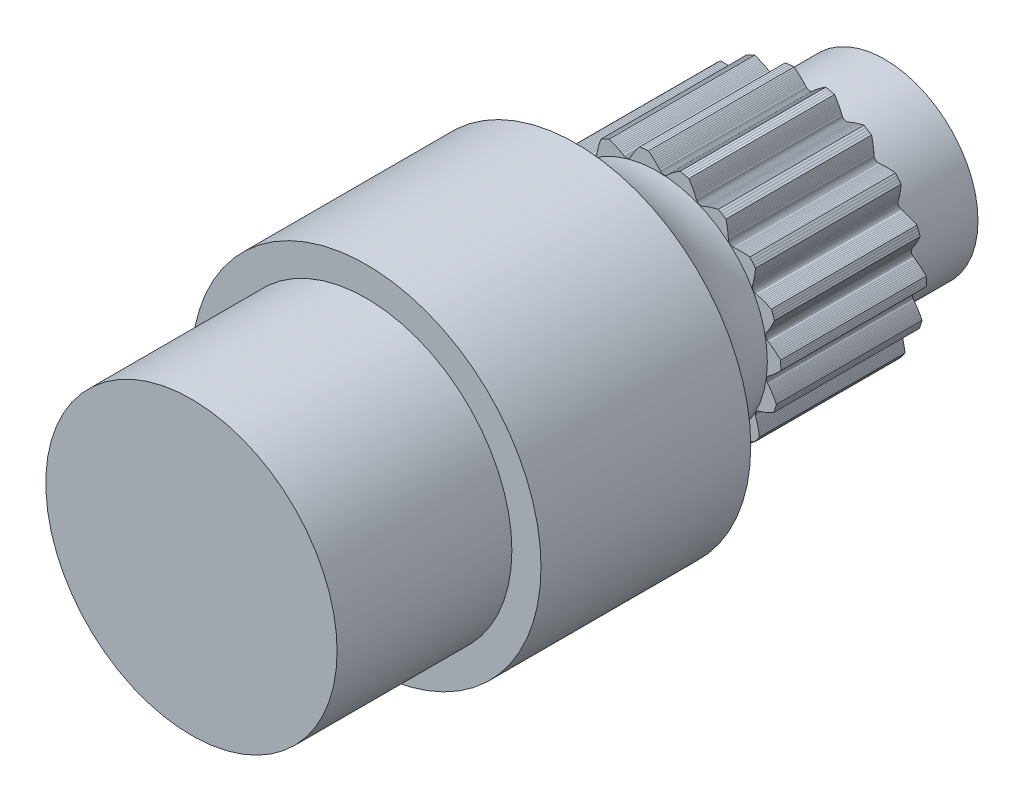
SolidWorks part; units mm, degrees
ref_plane "Front Plane" through (0, 0, 0) normal (0, 0, 1) x (1, 0, 0)
ref_plane "Top Plane" through (0, 0, 0) normal (0, 1, 0) x (1, 0, 0)
ref_plane "Right Plane" through (0, 0, 0) normal (1, 0, 0) x (0, 0, -1)
sketch "19T Shaft" plane through (0, 0, 0) normal (0, 0, 1) x (1, 0, 0)
  point P0 (-10.5755, 0)
  line B0 (6.0231, -8.6927) -> (5.8644, -8.8006)
  line B1 (5.8644, -8.8006) -> (5.7037, -8.9056)
  line B2 (5.7037, -8.9056) -> (5.5745, -8.8826)
  line B3 (5.5745, -8.8826) -> (5.4476, -8.8579)
  line B4 (5.4476, -8.8579) -> (5.3232, -8.8314)
  line B5 (5.3232, -8.8314) -> (5.1984, -8.8027)
  line B6 (5.1984, -8.8027) -> (5.0761, -8.7722)
  line B7 (5.0761, -8.7722) -> (4.9565, -8.7403)
  line B8 (4.9565, -8.7403) -> (4.8368, -8.706)
  line B9 (4.8368, -8.706) -> (4.7198, -8.6703)
  line B10 (4.7198, -8.6703) -> (4.603, -8.6323)
  line B11 (4.603, -8.6323) -> (4.4891, -8.593)
  line B12 (4.4891, -8.593) -> (4.3274, -8.5331)
  line B13 (4.3274, -8.5331) -> (4.2909, -8.5213)
  line B14 (4.2909, -8.5213) -> (4.254, -8.5136)
  line B15 (4.254, -8.5136) -> (4.2158, -8.5099)
  line B16 (4.2158, -8.5099) -> (4.1778, -8.5104)
  line B17 (4.1778, -8.5104) -> (4.1402, -8.515)
  line B18 (4.1402, -8.515) -> (4.1034, -8.5237)
  line B19 (4.1034, -8.5237) -> (4.0679, -8.5363)
  line B20 (4.0679, -8.5363) -> (4.0531, -8.5429)
  line B21 (4.0531, -8.5429) -> (4.0429, -8.5478)
  line B22 (4.0429, -8.5478) -> (4.0326, -8.5526)
  line B23 (4.0326, -8.5526) -> (4.0223, -8.5575)
  line B24 (4.0223, -8.5575) -> (4.012, -8.5623)
  line B25 (4.012, -8.5623) -> (3.9976, -8.5695)
  line B26 (3.9976, -8.5695) -> (3.9652, -8.5889)
  line B27 (3.9652, -8.5889) -> (3.9351, -8.6117)
  line B28 (3.9351, -8.6117) -> (3.9076, -8.6377)
  line B29 (3.9076, -8.6377) -> (3.883, -8.6668)
  line B30 (3.883, -8.6668) -> (3.8616, -8.6986)
  line B31 (3.8616, -8.6986) -> (3.8441, -8.732)
  line B32 (3.8441, -8.732) -> (3.83, -8.7676)
  line B33 (3.83, -8.7676) -> (3.7733, -8.9305)
  line B34 (3.7733, -8.9305) -> (3.7312, -9.0434)
  line B35 (3.7312, -9.0434) -> (3.6862, -9.1576)
  line B36 (3.6862, -9.1576) -> (3.6393, -9.2706)
  line B37 (3.6393, -9.2706) -> (3.5895, -9.3848)
  line B38 (3.5895, -9.3848) -> (3.5381, -9.4975)
  line B39 (3.5381, -9.4975) -> (3.4838, -9.6111)
  line B40 (3.4838, -9.6111) -> (3.4265, -9.7257)
  line B41 (3.4265, -9.7257) -> (3.3678, -9.8385)
  line B42 (3.3678, -9.8385) -> (3.3062, -9.9521)
  line B43 (3.3062, -9.9521) -> (3.2417, -10.0664)
  line B44 (3.2417, -10.0664) -> (3.0585, -10.1236)
  line B45 (3.0585, -10.1236) -> (2.8742, -10.1774)
  line B46 (8.5193, -6.266) -> (8.4042, -6.4196)
  line B47 (8.4042, -6.4196) -> (8.2863, -6.5711)
  line B48 (8.2863, -6.5711) -> (8.1566, -6.5913)
  line B49 (8.1566, -6.5913) -> (8.0286, -6.6091)
  line B50 (8.0286, -6.6091) -> (7.9024, -6.6245)
  line B51 (7.9024, -6.6245) -> (7.775, -6.6378)
  line B52 (7.775, -6.6378) -> (7.6495, -6.6487)
  line B53 (7.6495, -6.6487) -> (7.5259, -6.6573)
  line B54 (7.5259, -6.6573) -> (7.4015, -6.6638)
  line B55 (7.4015, -6.6638) -> (7.2793, -6.668)
  line B56 (7.2793, -6.668) -> (7.1565, -6.67)
  line B57 (7.1565, -6.67) -> (7.036, -6.6698)
  line B58 (7.036, -6.6698) -> (6.8636, -6.6657)
  line B59 (6.8636, -6.6657) -> (6.8253, -6.6663)
  line B60 (6.8253, -6.6663) -> (6.7879, -6.671)
  line B61 (6.7879, -6.671) -> (6.7506, -6.6799)
  line B62 (6.7506, -6.6799) -> (6.7147, -6.6927)
  line B63 (6.7147, -6.6927) -> (6.6807, -6.7093)
  line B64 (6.6807, -6.7093) -> (6.6487, -6.7295)
  line B65 (6.6487, -6.7295) -> (6.6192, -6.753)
  line B66 (6.6192, -6.753) -> (6.6074, -6.764)
  line B67 (6.6074, -6.764) -> (6.5993, -6.7719)
  line B68 (6.5993, -6.7719) -> (6.5911, -6.7798)
  line B69 (6.5911, -6.7798) -> (6.583, -6.7878)
  line B70 (6.583, -6.7878) -> (6.5748, -6.7957)
  line B71 (6.5748, -6.7957) -> (6.5635, -6.8072)
  line B72 (6.5635, -6.8072) -> (6.5392, -6.836)
  line B73 (6.5392, -6.836) -> (6.5181, -6.8673)
  line B74 (6.5181, -6.8673) -> (6.5006, -6.9009)
  line B75 (6.5006, -6.9009) -> (6.4867, -6.9364)
  line B76 (6.4867, -6.9364) -> (6.4768, -6.9734)
  line B77 (6.4768, -6.9734) -> (6.4711, -7.0107)
  line B78 (6.4711, -7.0107) -> (6.4693, -7.049)
  line B79 (6.4693, -7.049) -> (6.4686, -7.2215)
  line B80 (6.4686, -7.2215) -> (6.4654, -7.3419)
  line B81 (6.4654, -7.3419) -> (6.4599, -7.4646)
  line B82 (6.4599, -7.4646) -> (6.4523, -7.5866)
  line B83 (6.4523, -7.5866) -> (6.4423, -7.7108)
  line B84 (6.4423, -7.7108) -> (6.4302, -7.834)
  line B85 (6.4302, -7.834) -> (6.4157, -7.9592)
  line B86 (6.4157, -7.9592) -> (6.3988, -8.0862)
  line B87 (6.3988, -8.0862) -> (6.3799, -8.2119)
  line B88 (6.3799, -8.2119) -> (6.3585, -8.3394)
  line B89 (6.3585, -8.3394) -> (6.3346, -8.4684)
  line B90 (6.3346, -8.4684) -> (6.1799, -8.582)
  line B91 (6.1799, -8.582) -> (6.0231, -8.6927)
  line B92 (10.0923, -3.1603) -> (10.0332, -3.3429)
  line B93 (10.0332, -3.3429) -> (9.9709, -3.5245)
  line B94 (9.9709, -3.5245) -> (9.8549, -3.5857)
  line B95 (9.8549, -3.5857) -> (9.7396, -3.6441)
  line B96 (9.7396, -3.6441) -> (9.6252, -3.6997)
  line B97 (9.6252, -3.6997) -> (9.509, -3.7536)
  line B98 (9.509, -3.7536) -> (9.3938, -3.8047)
  line B99 (9.3938, -3.8047) -> (9.2797, -3.853)
  line B100 (9.2797, -3.853) -> (9.1642, -3.8995)
  line B101 (9.1642, -3.8995) -> (9.05, -3.9431)
  line B102 (9.05, -3.9431) -> (8.9345, -3.9849)
  line B103 (8.9345, -3.9849) -> (8.8205, -4.0238)
  line B104 (8.8205, -4.0238) -> (8.6561, -4.0759)
  line B105 (8.6561, -4.0759) -> (8.62, -4.089)
  line B106 (8.62, -4.089) -> (8.5862, -4.1055)
  line B107 (8.5862, -4.1055) -> (8.5538, -4.1261)
  line B108 (8.5538, -4.1261) -> (8.524, -4.1498)
  line B109 (8.524, -4.1498) -> (8.4972, -4.1766)
  line B110 (8.4972, -4.1766) -> (8.4735, -4.206)
  line B111 (8.4735, -4.206) -> (8.4533, -4.2378)
  line B112 (8.4533, -4.2378) -> (8.4457, -4.2521)
  line B113 (8.4457, -4.2521) -> (8.4405, -4.2622)
  line B114 (8.4405, -4.2622) -> (8.4354, -4.2723)
  line B115 (8.4354, -4.2723) -> (8.4303, -4.2825)
  line B116 (8.4303, -4.2825) -> (8.4251, -4.2926)
  line B117 (8.4251, -4.2926) -> (8.4181, -4.3072)
  line B118 (8.4181, -4.3072) -> (8.4045, -4.3423)
  line B119 (8.4045, -4.3423) -> (8.3948, -4.3788)
  line B120 (8.3948, -4.3788) -> (8.3891, -4.4163)
  line B121 (8.3891, -4.4163) -> (8.3875, -4.4543)
  line B122 (8.3875, -4.4543) -> (8.3902, -4.4926)
  line B123 (8.3902, -4.4926) -> (8.3968, -4.5297)
  line B124 (8.3968, -4.5297) -> (8.4076, -4.5665)
  line B125 (8.4076, -4.5665) -> (8.4629, -4.7298)
  line B126 (8.4629, -4.7298) -> (8.499, -4.8448)
  line B127 (8.499, -4.8448) -> (8.5336, -4.9626)
  line B128 (8.5336, -4.9626) -> (8.566, -5.0805)
  line B129 (8.566, -5.0805) -> (8.5969, -5.2012)
  line B130 (8.5969, -5.2012) -> (8.6255, -5.3217)
  line B131 (8.6255, -5.3217) -> (8.6525, -5.4448)
  line B132 (8.6525, -5.4448) -> (8.6777, -5.5704)
  line B133 (8.6777, -5.5704) -> (8.7006, -5.6954)
  line B134 (8.7006, -5.6954) -> (8.7218, -5.8229)
  line B135 (8.7218, -5.8229) -> (8.7411, -5.9527)
  line B136 (8.7411, -5.9527) -> (8.6316, -6.1104)
  line B137 (8.6316, -6.1104) -> (8.5193, -6.266)
  line B138 (10.5716, 0.2879) -> (10.5751, 0.096)
  line B139 (10.5751, 0.096) -> (10.5751, -0.096)
  line B140 (10.5751, -0.096) -> (10.4852, -0.1916)
  line B141 (10.4852, -0.1916) -> (10.3951, -0.2842)
  line B142 (10.3951, -0.2842) -> (10.3049, -0.3739)
  line B143 (10.3049, -0.3739) -> (10.2126, -0.4627)
  line B144 (10.2126, -0.4627) -> (10.1202, -0.5484)
  line B145 (10.1202, -0.5484) -> (10.028, -0.6311)
  line B146 (10.028, -0.6311) -> (9.9338, -0.7126)
  line B147 (9.9338, -0.7126) -> (9.8399, -0.791)
  line B148 (9.8399, -0.791) -> (9.7443, -0.868)
  line B149 (9.7443, -0.868) -> (9.6491, -0.9418)
  line B150 (9.6491, -0.9418) -> (9.5105, -1.0445)
  line B151 (9.5105, -1.0445) -> (9.4807, -1.0685)
  line B152 (9.4807, -1.0685) -> (9.454, -1.0952)
  line B153 (9.454, -1.0952) -> (9.43, -1.1251)
  line B154 (9.43, -1.1251) -> (9.4096, -1.1573)
  line B155 (9.4096, -1.1573) -> (9.3929, -1.1913)
  line B156 (9.3929, -1.1913) -> (9.3801, -1.2268)
  line B157 (9.3801, -1.2268) -> (9.3712, -1.2634)
  line B158 (9.3712, -1.2634) -> (9.3687, -1.2794)
  line B159 (9.3687, -1.2794) -> (9.3671, -1.2906)
  line B160 (9.3671, -1.2906) -> (9.3656, -1.3019)
  line B161 (9.3656, -1.3019) -> (9.364, -1.3131)
  line B162 (9.364, -1.3131) -> (9.3624, -1.3244)
  line B163 (9.3624, -1.3244) -> (9.3605, -1.3404)
  line B164 (9.3605, -1.3404) -> (9.3591, -1.3781)
  line B165 (9.3591, -1.3781) -> (9.3617, -1.4158)
  line B166 (9.3617, -1.4158) -> (9.3685, -1.4531)
  line B167 (9.3685, -1.4531) -> (9.3794, -1.4895)
  line B168 (9.3794, -1.4895) -> (9.3943, -1.5249)
  line B169 (9.3943, -1.5249) -> (9.4126, -1.5578)
  line B170 (9.4126, -1.5578) -> (9.4348, -1.5891)
  line B171 (9.4348, -1.5891) -> (9.5401, -1.7256)
  line B172 (9.5401, -1.7256) -> (9.6116, -1.8226)
  line B173 (9.6116, -1.8226) -> (9.6826, -1.9228)
  line B174 (9.6826, -1.9228) -> (9.7515, -2.0239)
  line B175 (9.7515, -2.0239) -> (9.8199, -2.128)
  line B176 (9.8199, -2.128) -> (9.8861, -2.2327)
  line B177 (9.8861, -2.2327) -> (9.9516, -2.3403)
  line B178 (9.9516, -2.3403) -> (10.0162, -2.4509)
  line B179 (10.0162, -2.4509) -> (10.0785, -2.5618)
  line B180 (10.0785, -2.5618) -> (10.1399, -2.6755)
  line B181 (10.1399, -2.6755) -> (10.2003, -2.792)
  line B182 (10.2003, -2.792) -> (10.1479, -2.9766)
  line B183 (10.1479, -2.9766) -> (10.0923, -3.1603)
  line B184 (9.9053, 3.7049) -> (9.9709, 3.5245)
  line B185 (9.9709, 3.5245) -> (10.0332, 3.3429)
  line B186 (10.0332, 3.3429) -> (9.9793, 3.2233)
  line B187 (9.9793, 3.2233) -> (9.9242, 3.1065)
  line B188 (9.9242, 3.1065) -> (9.868, 2.9924)
  line B189 (9.868, 2.9924) -> (9.8094, 2.8784)
  line B190 (9.8094, 2.8784) -> (9.7499, 2.7674)
  line B191 (9.7499, 2.7674) -> (9.6896, 2.6592)
  line B192 (9.6896, 2.6592) -> (9.627, 2.5516)
  line B193 (9.627, 2.5516) -> (9.5636, 2.4469)
  line B194 (9.5636, 2.4469) -> (9.4981, 2.343)
  line B195 (9.4981, 2.343) -> (9.4321, 2.2423)
  line B196 (9.4321, 2.2423) -> (9.3343, 2.1002)
  line B197 (9.3343, 2.1002) -> (9.3139, 2.0678)
  line B198 (9.3139, 2.0678) -> (9.2974, 2.0339)
  line B199 (9.2974, 2.0339) -> (9.2844, 1.9978)
  line B200 (9.2844, 1.9978) -> (9.2755, 1.9607)
  line B201 (9.2755, 1.9607) -> (9.2708, 1.9232)
  line B202 (9.2708, 1.9232) -> (9.2702, 1.8854)
  line B203 (9.2702, 1.8854) -> (9.2737, 1.8479)
  line B204 (9.2737, 1.8479) -> (9.2765, 1.832)
  line B205 (9.2765, 1.832) -> (9.2787, 1.8208)
  line B206 (9.2787, 1.8208) -> (9.2809, 1.8097)
  line B207 (9.2809, 1.8097) -> (9.283, 1.7985)
  line B208 (9.283, 1.7985) -> (9.2852, 1.7873)
  line B209 (9.2852, 1.7873) -> (9.2886, 1.7716)
  line B210 (9.2886, 1.7716) -> (9.2994, 1.7354)
  line B211 (9.2994, 1.7354) -> (9.3142, 1.7007)
  line B212 (9.3142, 1.7007) -> (9.3327, 1.6676)
  line B213 (9.3327, 1.6676) -> (9.3548, 1.6366)
  line B214 (9.3548, 1.6366) -> (9.3804, 1.6081)
  line B215 (9.3804, 1.6081) -> (9.4085, 1.5829)
  line B216 (9.4085, 1.5829) -> (9.4396, 1.5605)
  line B217 (9.4396, 1.5605) -> (9.5835, 1.4655)
  line B218 (9.5835, 1.4655) -> (9.6826, 1.397)
  line B219 (9.6826, 1.397) -> (9.7823, 1.3253)
  line B220 (9.7823, 1.3253) -> (9.8803, 1.2521)
  line B221 (9.8803, 1.2521) -> (9.9788, 1.1759)
  line B222 (9.9788, 1.1759) -> (10.0754, 1.0983)
  line B223 (10.0754, 1.0983) -> (10.1722, 1.0178)
  line B224 (10.1722, 1.0178) -> (10.2693, 0.9342)
  line B225 (10.2693, 0.9342) -> (10.3642, 0.8495)
  line B226 (10.3642, 0.8495) -> (10.4592, 0.7619)
  line B227 (10.4592, 0.7619) -> (10.5542, 0.6713)
  line B228 (10.5542, 0.6713) -> (10.5646, 0.4797)
  line B229 (10.5646, 0.4797) -> (10.5716, 0.2879)
  line B230 (8.1656, 6.7204) -> (8.2863, 6.5711)
  line B231 (8.2863, 6.5711) -> (8.4042, 6.4196)
  line B232 (8.4042, 6.4196) -> (8.392, 6.2889)
  line B233 (8.392, 6.2889) -> (8.3778, 6.1605)
  line B234 (8.3778, 6.1605) -> (8.3617, 6.0344)
  line B235 (8.3617, 6.0344) -> (8.3433, 5.9076)
  line B236 (8.3433, 5.9076) -> (8.3231, 5.7832)
  line B237 (8.3231, 5.7832) -> (8.3011, 5.6613)
  line B238 (8.3011, 5.6613) -> (8.2769, 5.5392)
  line B239 (8.2769, 5.5392) -> (8.2509, 5.4196)
  line B240 (8.2509, 5.4196) -> (8.2227, 5.3001)
  line B241 (8.2227, 5.3001) -> (8.193, 5.1834)
  line B242 (8.193, 5.1834) -> (8.1466, 5.0172)
  line B243 (8.1466, 5.0172) -> (8.1379, 4.9799)
  line B244 (8.1379, 4.9799) -> (8.1332, 4.9425)
  line B245 (8.1332, 4.9425) -> (8.1327, 4.9042)
  line B246 (8.1327, 4.9042) -> (8.1363, 4.8663)
  line B247 (8.1363, 4.8663) -> (8.144, 4.8292)
  line B248 (8.144, 4.8292) -> (8.1557, 4.7933)
  line B249 (8.1557, 4.7933) -> (8.1712, 4.7589)
  line B250 (8.1712, 4.7589) -> (8.179, 4.7448)
  line B251 (8.179, 4.7448) -> (8.1847, 4.7349)
  line B252 (8.1847, 4.7349) -> (8.1904, 4.7251)
  line B253 (8.1904, 4.7251) -> (8.1961, 4.7152)
  line B254 (8.1961, 4.7152) -> (8.2017, 4.7054)
  line B255 (8.2017, 4.7054) -> (8.2101, 4.6916)
  line B256 (8.2101, 4.6916) -> (8.2321, 4.6609)
  line B257 (8.2321, 4.6609) -> (8.2573, 4.6328)
  line B258 (8.2573, 4.6328) -> (8.2855, 4.6076)
  line B259 (8.2855, 4.6076) -> (8.3165, 4.5855)
  line B260 (8.3165, 4.5855) -> (8.35, 4.5667)
  line B261 (8.35, 4.5667) -> (8.3847, 4.552)
  line B262 (8.3847, 4.552) -> (8.4214, 4.541)
  line B263 (8.4214, 4.541) -> (8.5884, 4.4979)
  line B264 (8.5884, 4.4979) -> (8.7044, 4.4652)
  line B265 (8.7044, 4.4652) -> (8.822, 4.4298)
  line B266 (8.822, 4.4298) -> (8.9384, 4.3924)
  line B267 (8.9384, 4.3924) -> (9.0563, 4.3523)
  line B268 (9.0563, 4.3523) -> (9.1728, 4.3103)
  line B269 (9.1728, 4.3103) -> (9.2906, 4.2655)
  line B270 (9.2906, 4.2655) -> (9.4096, 4.218)
  line B271 (9.4096, 4.218) -> (9.5268, 4.1688)
  line B272 (9.5268, 4.1688) -> (9.6451, 4.1167)
  line B273 (9.6451, 4.1167) -> (9.7643, 4.0619)
  line B274 (9.7643, 4.0619) -> (9.8364, 3.884)
  line B275 (9.8364, 3.884) -> (9.9053, 3.7049)
  line B276 (5.5411, 9.0076) -> (5.7037, 8.9056)
  line B277 (5.7037, 8.9056) -> (5.8644, 8.8006)
  line B278 (5.8644, 8.8006) -> (5.8952, 8.6731)
  line B279 (5.8952, 8.6731) -> (5.9235, 8.547)
  line B280 (5.9235, 8.547) -> (5.9493, 8.4224)
  line B281 (5.9493, 8.4224) -> (5.9731, 8.2966)
  line B282 (5.9731, 8.2966) -> (5.9943, 8.1724)
  line B283 (5.9943, 8.1724) -> (6.0131, 8.0499)
  line B284 (6.0131, 8.0499) -> (6.0298, 7.9265)
  line B285 (6.0298, 7.9265) -> (6.0441, 7.8051)
  line B286 (6.0441, 7.8051) -> (6.0563, 7.6829)
  line B287 (6.0563, 7.6829) -> (6.066, 7.5628)
  line B288 (6.066, 7.5628) -> (6.0761, 7.3906)
  line B289 (6.0761, 7.3906) -> (6.0799, 7.3525)
  line B290 (6.0799, 7.3525) -> (6.0877, 7.3156)
  line B291 (6.0877, 7.3156) -> (6.0996, 7.2791)
  line B292 (6.0996, 7.2791) -> (6.1154, 7.2445)
  line B293 (6.1154, 7.2445) -> (6.1347, 7.2119)
  line B294 (6.1347, 7.2119) -> (6.1575, 7.1817)
  line B295 (6.1575, 7.1817) -> (6.1833, 7.1543)
  line B296 (6.1833, 7.1543) -> (6.1952, 7.1434)
  line B297 (6.1952, 7.1434) -> (6.2038, 7.1359)
  line B298 (6.2038, 7.1359) -> (6.2124, 7.1285)
  line B299 (6.2124, 7.1285) -> (6.221, 7.121)
  line B300 (6.221, 7.121) -> (6.2295, 7.1135)
  line B301 (6.2295, 7.1135) -> (6.2419, 7.1032)
  line B302 (6.2419, 7.1032) -> (6.2726, 7.0813)
  line B303 (6.2726, 7.0813) -> (6.3056, 7.063)
  line B304 (6.3056, 7.063) -> (6.3405, 7.0482)
  line B305 (6.3405, 7.0482) -> (6.377, 7.0374)
  line B306 (6.377, 7.0374) -> (6.4148, 7.0305)
  line B307 (6.4148, 7.0305) -> (6.4524, 7.0279)
  line B308 (6.4524, 7.0279) -> (6.4907, 7.0293)
  line B309 (6.4907, 7.0293) -> (6.6626, 7.0428)
  line B310 (6.6626, 7.0428) -> (6.7829, 7.0496)
  line B311 (6.7829, 7.0496) -> (6.9056, 7.0543)
  line B312 (6.9056, 7.0543) -> (7.0279, 7.0567)
  line B313 (7.0279, 7.0567) -> (7.1524, 7.057)
  line B314 (7.1524, 7.057) -> (7.2763, 7.0552)
  line B315 (7.2763, 7.0552) -> (7.4022, 7.0511)
  line B316 (7.4022, 7.0511) -> (7.5302, 7.0447)
  line B317 (7.5302, 7.0447) -> (7.657, 7.0362)
  line B318 (7.657, 7.0362) -> (7.7858, 7.0255)
  line B319 (7.7858, 7.0255) -> (7.9164, 7.0123)
  line B320 (7.9164, 7.0123) -> (8.0423, 6.8675)
  line B321 (8.0423, 6.8675) -> (8.1656, 6.7204)
  line B322 (2.3161, 10.3188) -> (2.503, 10.275)
  line B323 (2.503, 10.275) -> (2.6891, 10.2279)
  line B324 (2.6891, 10.2279) -> (2.7597, 10.1173)
  line B325 (2.7597, 10.1173) -> (2.8274, 10.0073)
  line B326 (2.8274, 10.0073) -> (2.8922, 9.8978)
  line B327 (2.8922, 9.8978) -> (2.9555, 9.7865)
  line B328 (2.9555, 9.7865) -> (3.016, 9.6759)
  line B329 (3.016, 9.6759) -> (3.0735, 9.5662)
  line B330 (3.0735, 9.5662) -> (3.1294, 9.4549)
  line B331 (3.1294, 9.4549) -> (3.1823, 9.3447)
  line B332 (3.1823, 9.3447) -> (3.2335, 9.233)
  line B333 (3.2335, 9.233) -> (3.2817, 9.1226)
  line B334 (3.2817, 9.1226) -> (3.3472, 8.9631)
  line B335 (3.3472, 8.9631) -> (3.3632, 8.9283)
  line B336 (3.3632, 8.9283) -> (3.3825, 8.8959)
  line B337 (3.3825, 8.8959) -> (3.4056, 8.8653)
  line B338 (3.4056, 8.8653) -> (3.4318, 8.8376)
  line B339 (3.4318, 8.8376) -> (3.4606, 8.8131)
  line B340 (3.4606, 8.8131) -> (3.4919, 8.7919)
  line B341 (3.4919, 8.7919) -> (3.5253, 8.7743)
  line B342 (3.5253, 8.7743) -> (3.5401, 8.7679)
  line B343 (3.5401, 8.7679) -> (3.5506, 8.7637)
  line B344 (3.5506, 8.7637) -> (3.5612, 8.7594)
  line B345 (3.5612, 8.7594) -> (3.5717, 8.7551)
  line B346 (3.5717, 8.7551) -> (3.5822, 8.7508)
  line B347 (3.5822, 8.7508) -> (3.5973, 8.7451)
  line B348 (3.5973, 8.7451) -> (3.6335, 8.7344)
  line B349 (3.6335, 8.7344) -> (3.6706, 8.7277)
  line B350 (3.6706, 8.7277) -> (3.7084, 8.7251)
  line B351 (3.7084, 8.7251) -> (3.7465, 8.7267)
  line B352 (3.7465, 8.7267) -> (3.7844, 8.7325)
  line B353 (3.7844, 8.7325) -> (3.8208, 8.7422)
  line B354 (3.8208, 8.7422) -> (3.8566, 8.756)
  line B355 (3.8566, 8.756) -> (4.0148, 8.8246)
  line B356 (4.0148, 8.8246) -> (4.1264, 8.87)
  line B357 (4.1264, 8.87) -> (4.2409, 8.9143)
  line B358 (4.2409, 8.9143) -> (4.3558, 8.9563)
  line B359 (4.3558, 8.9563) -> (4.4735, 8.997)
  line B360 (4.4735, 8.997) -> (4.5912, 9.0355)
  line B361 (4.5912, 9.0355) -> (4.7116, 9.0725)
  line B362 (4.7116, 9.0725) -> (4.8347, 9.1081)
  line B363 (4.8347, 9.1081) -> (4.9575, 9.1412)
  line B364 (4.9575, 9.1412) -> (5.0828, 9.1728)
  line B365 (5.0828, 9.1728) -> (5.2106, 9.2028)
  line B366 (5.2106, 9.2028) -> (5.3767, 9.1067)
  line B367 (5.3767, 9.1067) -> (5.5411, 9.0076)
  line B368 (-1.1599, 10.5117) -> (-0.9689, 10.531)
  line B369 (-0.9689, 10.531) -> (-0.7776, 10.5469)
  line B370 (-0.7776, 10.5469) -> (-0.6749, 10.4652)
  line B371 (-0.6749, 10.4652) -> (-0.5752, 10.3831)
  line B372 (-0.5752, 10.3831) -> (-0.4783, 10.3006)
  line B373 (-0.4783, 10.3006) -> (-0.3823, 10.2159)
  line B374 (-0.3823, 10.2159) -> (-0.2892, 10.1309)
  line B375 (-0.2892, 10.1309) -> (-0.1992, 10.0459)
  line B376 (-0.1992, 10.0459) -> (-0.1102, 9.9587)
  line B377 (-0.1102, 9.9587) -> (-0.0243, 9.8716)
  line B378 (-0.0243, 9.8716) -> (0.0603, 9.7827)
  line B379 (0.0603, 9.7827) -> (0.1418, 9.6939)
  line B380 (0.1418, 9.6939) -> (0.2555, 9.5643)
  line B381 (0.2555, 9.5643) -> (0.2819, 9.5365)
  line B382 (0.2819, 9.5365) -> (0.3107, 9.5122)
  line B383 (0.3107, 9.5122) -> (0.3425, 9.4907)
  line B384 (0.3425, 9.4907) -> (0.3763, 9.473)
  line B385 (0.3763, 9.473) -> (0.4115, 9.4592)
  line B386 (0.4115, 9.4592) -> (0.448, 9.4494)
  line B387 (0.448, 9.4494) -> (0.4852, 9.4436)
  line B388 (0.4852, 9.4436) -> (0.5013, 9.4423)
  line B389 (0.5013, 9.4423) -> (0.5127, 9.4417)
  line B390 (0.5127, 9.4417) -> (0.524, 9.4411)
  line B391 (0.524, 9.4411) -> (0.5354, 9.4405)
  line B392 (0.5354, 9.4405) -> (0.5467, 9.4398)
  line B393 (0.5467, 9.4398) -> (0.5629, 9.4393)
  line B394 (0.5629, 9.4393) -> (0.6005, 9.4409)
  line B395 (0.6005, 9.4409) -> (0.6379, 9.4467)
  line B396 (0.6379, 9.4467) -> (0.6744, 9.4565)
  line B397 (0.6744, 9.4565) -> (0.7099, 9.4703)
  line B398 (0.7099, 9.4703) -> (0.7439, 9.4881)
  line B399 (0.7439, 9.4881) -> (0.7752, 9.5091)
  line B400 (0.7752, 9.5091) -> (0.8045, 9.5338)
  line B401 (0.8045, 9.5338) -> (0.9319, 9.6501)
  line B402 (0.9319, 9.6501) -> (1.0227, 9.7293)
  line B403 (1.0227, 9.7293) -> (1.1167, 9.8083)
  line B404 (1.1167, 9.8083) -> (1.2117, 9.8854)
  line B405 (1.2117, 9.8854) -> (1.3098, 9.9621)
  line B406 (1.3098, 9.9621) -> (1.4086, 10.0367)
  line B407 (1.4086, 10.0367) -> (1.5105, 10.1108)
  line B408 (1.5105, 10.1108) -> (1.6154, 10.1844)
  line B409 (1.6154, 10.1844) -> (1.7207, 10.2556)
  line B410 (1.7207, 10.2556) -> (1.829, 10.3262)
  line B411 (1.829, 10.3262) -> (1.9401, 10.396)
  line B412 (1.9401, 10.396) -> (2.1285, 10.3591)
  line B413 (2.1285, 10.3591) -> (2.3161, 10.3188)
  line B414 (-4.5102, 9.5655) -> (-4.3358, 9.6458)
  line B415 (-4.3358, 9.6458) -> (-4.1601, 9.7229)
  line B416 (-4.1601, 9.7229) -> (-4.0364, 9.679)
  line B417 (-4.0364, 9.679) -> (-3.9154, 9.6337)
  line B418 (-3.9154, 9.6337) -> (-3.797, 9.5872)
  line B419 (-3.797, 9.5872) -> (-3.6786, 9.5382)
  line B420 (-3.6786, 9.5382) -> (-3.5631, 9.4881)
  line B421 (-3.5631, 9.4881) -> (-3.4503, 9.4369)
  line B422 (-3.4503, 9.4369) -> (-3.3378, 9.3834)
  line B423 (-3.3378, 9.3834) -> (-3.2283, 9.3289)
  line B424 (-3.2283, 9.3289) -> (-3.1194, 9.2722)
  line B425 (-3.1194, 9.2722) -> (-3.0135, 9.2147)
  line B426 (-3.0135, 9.2147) -> (-2.8638, 9.129)
  line B427 (-2.8638, 9.129) -> (-2.8298, 9.1113)
  line B428 (-2.8298, 9.1113) -> (-2.7947, 9.0977)
  line B429 (-2.7947, 9.0977) -> (-2.7577, 9.0877)
  line B430 (-2.7577, 9.0877) -> (-2.72, 9.0819)
  line B431 (-2.72, 9.0819) -> (-2.6822, 9.0803)
  line B432 (-2.6822, 9.0803) -> (-2.6445, 9.0828)
  line B433 (-2.6445, 9.0828) -> (-2.6074, 9.0894)
  line B434 (-2.6074, 9.0894) -> (-2.5917, 9.0935)
  line B435 (-2.5917, 9.0935) -> (-2.5808, 9.0966)
  line B436 (-2.5808, 9.0966) -> (-2.5699, 9.0997)
  line B437 (-2.5699, 9.0997) -> (-2.5589, 9.1028)
  line B438 (-2.5589, 9.1028) -> (-2.548, 9.1059)
  line B439 (-2.548, 9.1059) -> (-2.5325, 9.1106)
  line B440 (-2.5325, 9.1106) -> (-2.4975, 9.1244)
  line B441 (-2.4975, 9.1244) -> (-2.464, 9.1419)
  line B442 (-2.464, 9.1419) -> (-2.4326, 9.1631)
  line B443 (-2.4326, 9.1631) -> (-2.4036, 9.1877)
  line B444 (-2.4036, 9.1877) -> (-2.3772, 9.2156)
  line B445 (-2.3772, 9.2156) -> (-2.3544, 9.2456)
  line B446 (-2.3544, 9.2456) -> (-2.3347, 9.2785)
  line B447 (-2.3347, 9.2785) -> (-2.2519, 9.4298)
  line B448 (-2.2519, 9.4298) -> (-2.1918, 9.5342)
  line B449 (-2.1918, 9.5342) -> (-2.1286, 9.6395)
  line B450 (-2.1286, 9.6395) -> (-2.0638, 9.7432)
  line B451 (-2.0638, 9.7432) -> (-1.9959, 9.8476)
  line B452 (-1.9959, 9.8476) -> (-1.9266, 9.9503)
  line B453 (-1.9266, 9.9503) -> (-1.8543, 10.0535)
  line B454 (-1.8543, 10.0535) -> (-1.779, 10.1571)
  line B455 (-1.779, 10.1571) -> (-1.7025, 10.2587)
  line B456 (-1.7025, 10.2587) -> (-1.623, 10.3606)
  line B457 (-1.623, 10.3606) -> (-1.5406, 10.4627)
  line B458 (-1.5406, 10.4627) -> (-1.3505, 10.4889)
  line B459 (-1.3505, 10.4889) -> (-1.1599, 10.5117)
  line B460 (-7.3717, 7.5828) -> (-7.2329, 7.7153)
  line B461 (-7.2329, 7.7153) -> (-7.0917, 7.8453)
  line B462 (-7.0917, 7.8453) -> (-6.9605, 7.844)
  line B463 (-6.9605, 7.844) -> (-6.8313, 7.8404)
  line B464 (-6.8313, 7.8404) -> (-6.7042, 7.8348)
  line B465 (-6.7042, 7.8348) -> (-6.5764, 7.827)
  line B466 (-6.5764, 7.827) -> (-6.4508, 7.8171)
  line B467 (-6.4508, 7.8171) -> (-6.3275, 7.8052)
  line B468 (-6.3275, 7.8052) -> (-6.2037, 7.7912)
  line B469 (-6.2037, 7.7912) -> (-6.0825, 7.7752)
  line B470 (-6.0825, 7.7752) -> (-5.961, 7.757)
  line B471 (-5.961, 7.757) -> (-5.8422, 7.7369)
  line B472 (-5.8422, 7.7369) -> (-5.6729, 7.7045)
  line B473 (-5.6729, 7.7045) -> (-5.635, 7.6988)
  line B474 (-5.635, 7.6988) -> (-5.5973, 7.6973)
  line B475 (-5.5973, 7.6973) -> (-5.559, 7.6999)
  line B476 (-5.559, 7.6999) -> (-5.5215, 7.7067)
  line B477 (-5.5215, 7.7067) -> (-5.4852, 7.7174)
  line B478 (-5.4852, 7.7174) -> (-5.4504, 7.732)
  line B479 (-5.4504, 7.732) -> (-5.4174, 7.7503)
  line B480 (-5.4174, 7.7503) -> (-5.404, 7.7593)
  line B481 (-5.404, 7.7593) -> (-5.3946, 7.7658)
  line B482 (-5.3946, 7.7658) -> (-5.3853, 7.7722)
  line B483 (-5.3853, 7.7722) -> (-5.376, 7.7787)
  line B484 (-5.376, 7.7787) -> (-5.3666, 7.7852)
  line B485 (-5.3666, 7.7852) -> (-5.3535, 7.7946)
  line B486 (-5.3535, 7.7946) -> (-5.3248, 7.8191)
  line B487 (-5.3248, 7.8191) -> (-5.2989, 7.8465)
  line B488 (-5.2989, 7.8465) -> (-5.2761, 7.8768)
  line B489 (-5.2761, 7.8768) -> (-5.2566, 7.9095)
  line B490 (-5.2566, 7.9095) -> (-5.2407, 7.9444)
  line B491 (-5.2407, 7.9444) -> (-5.2289, 7.9802)
  line B492 (-5.2289, 7.9802) -> (-5.2209, 8.0177)
  line B493 (-5.2209, 8.0177) -> (-5.1918, 8.1877)
  line B494 (-5.1918, 8.1877) -> (-5.1688, 8.3059)
  line B495 (-5.1688, 8.3059) -> (-5.1432, 8.426)
  line B496 (-5.1432, 8.426) -> (-5.1155, 8.5452)
  line B497 (-5.1155, 8.5452) -> (-5.0853, 8.666)
  line B498 (-5.0853, 8.666) -> (-5.0531, 8.7856)
  line B499 (-5.0531, 8.7856) -> (-5.0182, 8.9066)
  line B500 (-5.0182, 8.9066) -> (-4.9806, 9.0291)
  line B501 (-4.9806, 9.0291) -> (-4.9412, 9.15)
  line B502 (-4.9412, 9.15) -> (-4.8992, 9.2722)
  line B503 (-4.8992, 9.2722) -> (-4.8544, 9.3956)
  line B504 (-4.8544, 9.3956) -> (-4.683, 9.4821)
  line B505 (-4.683, 9.4821) -> (-4.5102, 9.5655)
  line B506 (-9.4344, 4.7783) -> (-9.3462, 4.9488)
  line B507 (-9.3462, 4.9488) -> (-9.2548, 5.1176)
  line B508 (-9.2548, 5.1176) -> (-9.1303, 5.1589)
  line B509 (-9.1303, 5.1589) -> (-9.007, 5.1975)
  line B510 (-9.007, 5.1975) -> (-8.885, 5.2334)
  line B511 (-8.885, 5.2334) -> (-8.7615, 5.2675)
  line B512 (-8.7615, 5.2675) -> (-8.6395, 5.299)
  line B513 (-8.6395, 5.299) -> (-8.519, 5.3278)
  line B514 (-8.519, 5.3278) -> (-8.3974, 5.3547)
  line B515 (-8.3974, 5.3547) -> (-8.2775, 5.3789)
  line B516 (-8.2775, 5.3789) -> (-8.1567, 5.4011)
  line B517 (-8.1567, 5.4011) -> (-8.0379, 5.4208)
  line B518 (-8.0379, 5.4208) -> (-7.8671, 5.4451)
  line B519 (-7.8671, 5.4451) -> (-7.8294, 5.452)
  line B520 (-7.8294, 5.452) -> (-7.7933, 5.4628)
  line B521 (-7.7933, 5.4628) -> (-7.758, 5.4777)
  line B522 (-7.758, 5.4777) -> (-7.7247, 5.4963)
  line B523 (-7.7247, 5.4963) -> (-7.6939, 5.5182)
  line B524 (-7.6939, 5.5182) -> (-7.6657, 5.5434)
  line B525 (-7.6657, 5.5434) -> (-7.6404, 5.5714)
  line B526 (-7.6404, 5.5714) -> (-7.6306, 5.5842)
  line B527 (-7.6306, 5.5842) -> (-7.6239, 5.5933)
  line B528 (-7.6239, 5.5933) -> (-7.6172, 5.6025)
  line B529 (-7.6172, 5.6025) -> (-7.6104, 5.6117)
  line B530 (-7.6104, 5.6117) -> (-7.6037, 5.6208)
  line B531 (-7.6037, 5.6208) -> (-7.5944, 5.634)
  line B532 (-7.5944, 5.634) -> (-7.5751, 5.6664)
  line B533 (-7.5751, 5.6664) -> (-7.5596, 5.7008)
  line B534 (-7.5596, 5.7008) -> (-7.5478, 5.7368)
  line B535 (-7.5478, 5.7368) -> (-7.54, 5.7741)
  line B536 (-7.54, 5.7741) -> (-7.5363, 5.8123)
  line B537 (-7.5363, 5.8123) -> (-7.5367, 5.85)
  line B538 (-7.5367, 5.85) -> (-7.5413, 5.888)
  line B539 (-7.5413, 5.888) -> (-7.569, 6.0583)
  line B540 (-7.569, 6.0583) -> (-7.5856, 6.1776)
  line B541 (-7.5856, 6.1776) -> (-7.6004, 6.2995)
  line B542 (-7.6004, 6.2995) -> (-7.613, 6.4212)
  line B543 (-7.613, 6.4212) -> (-7.6236, 6.5452)
  line B544 (-7.6236, 6.5452) -> (-7.6319, 6.6688)
  line B545 (-7.6319, 6.6688) -> (-7.6383, 6.7946)
  line B546 (-7.6383, 6.7946) -> (-7.6425, 6.9227)
  line B547 (-7.6425, 6.9227) -> (-7.6445, 7.0498)
  line B548 (-7.6445, 7.0498) -> (-7.6444, 7.1791)
  line B549 (-7.6444, 7.1791) -> (-7.6421, 7.3103)
  line B550 (-7.6421, 7.3103) -> (-7.5081, 7.4478)
  line B551 (-7.5081, 7.4478) -> (-7.3717, 7.5828)
  line B552 (-10.4748, 1.4561) -> (-10.4466, 1.6459)
  line B553 (-10.4466, 1.6459) -> (-10.415, 1.8353)
  line B554 (-10.415, 1.8353) -> (-10.3106, 1.9148)
  line B555 (-10.3106, 1.9148) -> (-10.2066, 1.9913)
  line B556 (-10.2066, 1.9913) -> (-10.1028, 2.0649)
  line B557 (-10.1028, 2.0649) -> (-9.9971, 2.1373)
  line B558 (-9.9971, 2.1373) -> (-9.8919, 2.2066)
  line B559 (-9.8919, 2.2066) -> (-9.7874, 2.273)
  line B560 (-9.7874, 2.273) -> (-9.6811, 2.3379)
  line B561 (-9.6811, 2.3379) -> (-9.5755, 2.3998)
  line B562 (-9.5755, 2.3998) -> (-9.4685, 2.46)
  line B563 (-9.4685, 2.46) -> (-9.3625, 2.5172)
  line B564 (-9.3625, 2.5172) -> (-9.2089, 2.5956)
  line B565 (-9.2089, 2.5956) -> (-9.1755, 2.6144)
  line B566 (-9.1755, 2.6144) -> (-9.1448, 2.6363)
  line B567 (-9.1448, 2.6363) -> (-9.1162, 2.6619)
  line B568 (-9.1162, 2.6619) -> (-9.0908, 2.6902)
  line B569 (-9.0908, 2.6902) -> (-9.0687, 2.721)
  line B570 (-9.0687, 2.721) -> (-9.0503, 2.754)
  line B571 (-9.0503, 2.754) -> (-9.0355, 2.7886)
  line B572 (-9.0355, 2.7886) -> (-9.0303, 2.804)
  line B573 (-9.0303, 2.804) -> (-9.027, 2.8148)
  line B574 (-9.027, 2.8148) -> (-9.0236, 2.8257)
  line B575 (-9.0236, 2.8257) -> (-9.0202, 2.8365)
  line B576 (-9.0202, 2.8365) -> (-9.0167, 2.8473)
  line B577 (-9.0167, 2.8473) -> (-9.0122, 2.8629)
  line B578 (-9.0122, 2.8629) -> (-9.0046, 2.8998)
  line B579 (-9.0046, 2.8998) -> (-9.001, 2.9374)
  line B580 (-9.001, 2.9374) -> (-9.0016, 2.9752)
  line B581 (-9.0016, 2.9752) -> (-9.0063, 3.013)
  line B582 (-9.0063, 3.013) -> (-9.0152, 3.0503)
  line B583 (-9.0152, 3.0503) -> (-9.0279, 3.0858)
  line B584 (-9.0279, 3.0858) -> (-9.0446, 3.1203)
  line B585 (-9.0446, 3.1203) -> (-9.126, 3.2724)
  line B586 (-9.126, 3.2724) -> (-9.1805, 3.3798)
  line B587 (-9.1805, 3.3798) -> (-9.2341, 3.4903)
  line B588 (-9.2341, 3.4903) -> (-9.2854, 3.6013)
  line B589 (-9.2854, 3.6013) -> (-9.3357, 3.7152)
  line B590 (-9.3357, 3.7152) -> (-9.3838, 3.8294)
  line B591 (-9.3838, 3.8294) -> (-9.4306, 3.9463)
  line B592 (-9.4306, 3.9463) -> (-9.4762, 4.0661)
  line B593 (-9.4762, 4.0661) -> (-9.5194, 4.1857)
  line B594 (-9.5194, 4.1857) -> (-9.5612, 4.3079)
  line B595 (-9.5612, 4.3079) -> (-9.6016, 4.4328)
  line B596 (-9.6016, 4.4328) -> (-9.5196, 4.6063)
  line B597 (-9.5196, 4.6063) -> (-9.4344, 4.7783)
  line B598 (-10.38, -2.024) -> (-10.415, -1.8353)
  line B599 (-10.415, -1.8353) -> (-10.4466, -1.6459)
  line B600 (-10.4466, -1.6459) -> (-10.3737, -1.5368)
  line B601 (-10.3737, -1.5368) -> (-10.3001, -1.4306)
  line B602 (-10.3001, -1.4306) -> (-10.2259, -1.3273)
  line B603 (-10.2259, -1.3273) -> (-10.1494, -1.2246)
  line B604 (-10.1494, -1.2246) -> (-10.0725, -1.1248)
  line B605 (-10.0725, -1.1248) -> (-9.9951, -1.0281)
  line B606 (-9.9951, -1.0281) -> (-9.9156, -0.9322)
  line B607 (-9.9156, -0.9322) -> (-9.8359, -0.8394)
  line B608 (-9.8359, -0.8394) -> (-9.7543, -0.7477)
  line B609 (-9.7543, -0.7477) -> (-9.6725, -0.6592)
  line B610 (-9.6725, -0.6592) -> (-9.5527, -0.5352)
  line B611 (-9.5527, -0.5352) -> (-9.5272, -0.5065)
  line B612 (-9.5272, -0.5065) -> (-9.5053, -0.4758)
  line B613 (-9.5053, -0.4758) -> (-9.4866, -0.4424)
  line B614 (-9.4866, -0.4424) -> (-9.4718, -0.4073)
  line B615 (-9.4718, -0.4073) -> (-9.4609, -0.371)
  line B616 (-9.4609, -0.371) -> (-9.4541, -0.3339)
  line B617 (-9.4541, -0.3339) -> (-9.4514, -0.2963)
  line B618 (-9.4514, -0.2963) -> (-9.4515, -0.2801)
  line B619 (-9.4515, -0.2801) -> (-9.4518, -0.2688)
  line B620 (-9.4518, -0.2688) -> (-9.4521, -0.2574)
  line B621 (-9.4521, -0.2574) -> (-9.4524, -0.246)
  line B622 (-9.4524, -0.246) -> (-9.4527, -0.2347)
  line B623 (-9.4527, -0.2347) -> (-9.4535, -0.2185)
  line B624 (-9.4535, -0.2185) -> (-9.4583, -0.1811)
  line B625 (-9.4583, -0.1811) -> (-9.4671, -0.1444)
  line B626 (-9.4671, -0.1444) -> (-9.4799, -0.1088)
  line B627 (-9.4799, -0.1088) -> (-9.4966, -0.0746)
  line B628 (-9.4966, -0.0746) -> (-9.5172, -0.0422)
  line B629 (-9.5172, -0.0422) -> (-9.5407, -0.0127)
  line B630 (-9.5407, -0.0127) -> (-9.5677, 0.0145)
  line B631 (-9.5677, 0.0145) -> (-9.6941, 0.1319)
  line B632 (-9.6941, 0.1319) -> (-9.7805, 0.2158)
  line B633 (-9.7805, 0.2158) -> (-9.867, 0.3029)
  line B634 (-9.867, 0.3029) -> (-9.9517, 0.3912)
  line B635 (-9.9517, 0.3912) -> (-10.0362, 0.4826)
  line B636 (-10.0362, 0.4826) -> (-10.1187, 0.575)
  line B637 (-10.1187, 0.575) -> (-10.201, 0.6704)
  line B638 (-10.201, 0.6704) -> (-10.283, 0.7688)
  line B639 (-10.283, 0.7688) -> (-10.3627, 0.868)
  line B640 (-10.3627, 0.868) -> (-10.442, 0.97)
  line B641 (-10.442, 0.97) -> (-10.5207, 1.075)
  line B642 (-10.5207, 1.075) -> (-10.4995, 1.2657)
  line B643 (-10.4995, 1.2657) -> (-10.4748, 1.4561)
  line B644 (-9.1604, -5.2847) -> (-9.2548, -5.1176)
  line B645 (-9.2548, -5.1176) -> (-9.3462, -4.9488)
  line B646 (-9.3462, -4.9488) -> (-9.3126, -4.8219)
  line B647 (-9.3126, -4.8219) -> (-9.2775, -4.6976)
  line B648 (-9.2775, -4.6976) -> (-9.2409, -4.5758)
  line B649 (-9.2409, -4.5758) -> (-9.2019, -4.4537)
  line B650 (-9.2019, -4.4537) -> (-9.1615, -4.3344)
  line B651 (-9.1615, -4.3344) -> (-9.1197, -4.2178)
  line B652 (-9.1197, -4.2178) -> (-9.0757, -4.1013)
  line B653 (-9.0757, -4.1013) -> (-9.0304, -3.9877)
  line B654 (-9.0304, -3.9877) -> (-8.983, -3.8744)
  line B655 (-8.983, -3.8744) -> (-8.9344, -3.7642)
  line B656 (-8.9344, -3.7642) -> (-8.8613, -3.6079)
  line B657 (-8.8613, -3.6079) -> (-8.8465, -3.5726)
  line B658 (-8.8465, -3.5726) -> (-8.8358, -3.5364)
  line B659 (-8.8358, -3.5364) -> (-8.829, -3.4987)
  line B660 (-8.829, -3.4987) -> (-8.8263, -3.4607)
  line B661 (-8.8263, -3.4607) -> (-8.8278, -3.4229)
  line B662 (-8.8278, -3.4229) -> (-8.8334, -3.3855)
  line B663 (-8.8334, -3.3855) -> (-8.8431, -3.3491)
  line B664 (-8.8431, -3.3491) -> (-8.8484, -3.3338)
  line B665 (-8.8484, -3.3338) -> (-8.8524, -3.3232)
  line B666 (-8.8524, -3.3232) -> (-8.8564, -3.3125)
  line B667 (-8.8564, -3.3125) -> (-8.8604, -3.3019)
  line B668 (-8.8604, -3.3019) -> (-8.8644, -3.2912)
  line B669 (-8.8644, -3.2912) -> (-8.8703, -3.2762)
  line B670 (-8.8703, -3.2762) -> (-8.887, -3.2424)
  line B671 (-8.887, -3.2424) -> (-8.9072, -3.2105)
  line B672 (-8.9072, -3.2105) -> (-8.9309, -3.181)
  line B673 (-8.9309, -3.181) -> (-8.9579, -3.1541)
  line B674 (-8.9579, -3.1541) -> (-8.9878, -3.1301)
  line B675 (-8.9878, -3.1301) -> (-9.0196, -3.1099)
  line B676 (-9.0196, -3.1099) -> (-9.054, -3.0929)
  line B677 (-9.054, -3.0929) -> (-9.2116, -3.0229)
  line B678 (-9.2116, -3.0229) -> (-9.3206, -2.9716)
  line B679 (-9.3206, -2.9716) -> (-9.4308, -2.9173)
  line B680 (-9.4308, -2.9173) -> (-9.5395, -2.8613)
  line B681 (-9.5395, -2.8613) -> (-9.6492, -2.8023)
  line B682 (-9.6492, -2.8023) -> (-9.7572, -2.7417)
  line B683 (-9.7572, -2.7417) -> (-9.866, -2.6782)
  line B684 (-9.866, -2.6782) -> (-9.9755, -2.6117)
  line B685 (-9.9755, -2.6117) -> (-10.0831, -2.5438)
  line B686 (-10.0831, -2.5438) -> (-10.1912, -2.4731)
  line B687 (-10.1912, -2.4731) -> (-10.2997, -2.3993)
  line B688 (-10.2997, -2.3993) -> (-10.3416, -2.212)
  line B689 (-10.3416, -2.212) -> (-10.38, -2.024)
  line B690 (-6.9481, -7.9727) -> (-7.0917, -7.8453)
  line B691 (-7.0917, -7.8453) -> (-7.2329, -7.7153)
  line B692 (-7.2329, -7.7153) -> (-7.2424, -7.5844)
  line B693 (-7.2424, -7.5844) -> (-7.2495, -7.4554)
  line B694 (-7.2495, -7.4554) -> (-7.2544, -7.3283)
  line B695 (-7.2544, -7.3283) -> (-7.2572, -7.2003)
  line B696 (-7.2572, -7.2003) -> (-7.2577, -7.0743)
  line B697 (-7.2577, -7.0743) -> (-7.2561, -6.9504)
  line B698 (-7.2561, -6.9504) -> (-7.2522, -6.8259)
  line B699 (-7.2522, -6.8259) -> (-7.2463, -6.7038)
  line B700 (-7.2463, -6.7038) -> (-7.2382, -6.5812)
  line B701 (-7.2382, -6.5812) -> (-7.2281, -6.4612)
  line B702 (-7.2281, -6.4612) -> (-7.2097, -6.2897)
  line B703 (-7.2097, -6.2897) -> (-7.2072, -6.2515)
  line B704 (-7.2072, -6.2515) -> (-7.2088, -6.2138)
  line B705 (-7.2088, -6.2138) -> (-7.2146, -6.1759)
  line B706 (-7.2146, -6.1759) -> (-7.2244, -6.1391)
  line B707 (-7.2244, -6.1391) -> (-7.2381, -6.1038)
  line B708 (-7.2381, -6.1038) -> (-7.2555, -6.0703)
  line B709 (-7.2555, -6.0703) -> (-7.2765, -6.039)
  line B710 (-7.2765, -6.039) -> (-7.2865, -6.0263)
  line B711 (-7.2865, -6.0263) -> (-7.2937, -6.0175)
  line B712 (-7.2937, -6.0175) -> (-7.301, -6.0087)
  line B713 (-7.301, -6.0087) -> (-7.3082, -6)
  line B714 (-7.3082, -6) -> (-7.3154, -5.9912)
  line B715 (-7.3154, -5.9912) -> (-7.3259, -5.9789)
  line B716 (-7.3259, -5.9789) -> (-7.3526, -5.9523)
  line B717 (-7.3526, -5.9523) -> (-7.3821, -5.9288)
  line B718 (-7.3821, -5.9288) -> (-7.4142, -5.9085)
  line B719 (-7.4142, -5.9085) -> (-7.4484, -5.8918)
  line B720 (-7.4484, -5.8918) -> (-7.4845, -5.8788)
  line B721 (-7.4845, -5.8788) -> (-7.5211, -5.87)
  line B722 (-7.5211, -5.87) -> (-7.5591, -5.8651)
  line B723 (-7.5591, -5.8651) -> (-7.731, -5.8502)
  line B724 (-7.731, -5.8502) -> (-7.8507, -5.837)
  line B725 (-7.8507, -5.837) -> (-7.9725, -5.8214)
  line B726 (-7.9725, -5.8214) -> (-8.0935, -5.8037)
  line B727 (-8.0935, -5.8037) -> (-8.2164, -5.7835)
  line B728 (-8.2164, -5.7835) -> (-8.3383, -5.7613)
  line B729 (-8.3383, -5.7613) -> (-8.4618, -5.7366)
  line B730 (-8.4618, -5.7366) -> (-8.587, -5.7092)
  line B731 (-8.587, -5.7092) -> (-8.7107, -5.68)
  line B732 (-8.7107, -5.68) -> (-8.836, -5.6481)
  line B733 (-8.836, -5.6481) -> (-8.9626, -5.6137)
  line B734 (-8.9626, -5.6137) -> (-9.063, -5.4501)
  line B735 (-9.063, -5.4501) -> (-9.1604, -5.2847)
  line B736 (-3.9829, -9.7968) -> (-4.1601, -9.7229)
  line B737 (-4.1601, -9.7229) -> (-4.3358, -9.6458)
  line B738 (-4.3358, -9.6458) -> (-4.3873, -9.5251)
  line B739 (-4.3873, -9.5251) -> (-4.436, -9.4054)
  line B740 (-4.436, -9.4054) -> (-4.4819, -9.2868)
  line B741 (-4.4819, -9.2868) -> (-4.526, -9.1665)
  line B742 (-4.526, -9.1665) -> (-4.5674, -9.0475)
  line B743 (-4.5674, -9.0475) -> (-4.6061, -8.9299)
  line B744 (-4.6061, -8.9299) -> (-4.6429, -8.8109)
  line B745 (-4.6429, -8.8109) -> (-4.677, -8.6934)
  line B746 (-4.677, -8.6934) -> (-4.7091, -8.5749)
  line B747 (-4.7091, -8.5749) -> (-4.7385, -8.4581)
  line B748 (-4.7385, -8.4581) -> (-4.7768, -8.2899)
  line B749 (-4.7768, -8.2899) -> (-4.7868, -8.2529)
  line B750 (-4.7868, -8.2529) -> (-4.8006, -8.2178)
  line B751 (-4.8006, -8.2178) -> (-4.8183, -8.1838)
  line B752 (-4.8183, -8.1838) -> (-4.8396, -8.1522)
  line B753 (-4.8396, -8.1522) -> (-4.864, -8.1233)
  line B754 (-4.864, -8.1233) -> (-4.8914, -8.0973)
  line B755 (-4.8914, -8.0973) -> (-4.9214, -8.0744)
  line B756 (-4.9214, -8.0744) -> (-4.935, -8.0657)
  line B757 (-4.935, -8.0657) -> (-4.9447, -8.0597)
  line B758 (-4.9447, -8.0597) -> (-4.9543, -8.0538)
  line B759 (-4.9543, -8.0538) -> (-4.964, -8.0478)
  line B760 (-4.964, -8.0478) -> (-4.9737, -8.0419)
  line B761 (-4.9737, -8.0419) -> (-4.9876, -8.0337)
  line B762 (-4.9876, -8.0337) -> (-5.0215, -8.0172)
  line B763 (-5.0215, -8.0172) -> (-5.0571, -8.0045)
  line B764 (-5.0571, -8.0045) -> (-5.0939, -7.9957)
  line B765 (-5.0939, -7.9957) -> (-5.1317, -7.991)
  line B766 (-5.1317, -7.991) -> (-5.1701, -7.9905)
  line B767 (-5.1701, -7.9905) -> (-5.2076, -7.9941)
  line B768 (-5.2076, -7.9941) -> (-5.2452, -8.0018)
  line B769 (-5.2452, -8.0018) -> (-5.4125, -8.0434)
  line B770 (-5.4125, -8.0434) -> (-5.5301, -8.0699)
  line B771 (-5.5301, -8.0699) -> (-5.6503, -8.0947)
  line B772 (-5.6503, -8.0947) -> (-5.7705, -8.1172)
  line B773 (-5.7705, -8.1172) -> (-5.8933, -8.138)
  line B774 (-5.8933, -8.138) -> (-6.0158, -8.1566)
  line B775 (-6.0158, -8.1566) -> (-6.1407, -8.1733)
  line B776 (-6.1407, -8.1733) -> (-6.2679, -8.1881)
  line B777 (-6.2679, -8.1881) -> (-6.3945, -8.2006)
  line B778 (-6.3945, -8.2006) -> (-6.5233, -8.2111)
  line B779 (-6.5233, -8.2111) -> (-6.6542, -8.2196)
  line B780 (-6.6542, -8.2196) -> (-6.8023, -8.0975)
  line B781 (-6.8023, -8.0975) -> (-6.9481, -7.9727)
  line B782 (-0.5861, -10.5592) -> (-0.7776, -10.5469)
  line B783 (-0.7776, -10.5469) -> (-0.9689, -10.531)
  line B784 (-0.9689, -10.531) -> (-1.0568, -10.4335)
  line B785 (-1.0568, -10.4335) -> (-1.1417, -10.3361)
  line B786 (-1.1417, -10.3361) -> (-1.2236, -10.2389)
  line B787 (-1.2236, -10.2389) -> (-1.3044, -10.1395)
  line B788 (-1.3044, -10.1395) -> (-1.3822, -10.0404)
  line B789 (-1.3822, -10.0404) -> (-1.457, -9.9416)
  line B790 (-1.457, -9.9416) -> (-1.5305, -9.8411)
  line B791 (-1.5305, -9.8411) -> (-1.6008, -9.741)
  line B792 (-1.6008, -9.741) -> (-1.6697, -9.6393)
  line B793 (-1.6697, -9.6393) -> (-1.7354, -9.5384)
  line B794 (-1.7354, -9.5384) -> (-1.8263, -9.3918)
  line B795 (-1.8263, -9.3918) -> (-1.8478, -9.36)
  line B796 (-1.8478, -9.36) -> (-1.8721, -9.3313)
  line B797 (-1.8721, -9.3313) -> (-1.9, -9.3049)
  line B798 (-1.9, -9.3049) -> (-1.9303, -9.2819)
  line B799 (-1.9303, -9.2819) -> (-1.9629, -9.2625)
  line B800 (-1.9629, -9.2625) -> (-1.9972, -9.2468)
  line B801 (-1.9972, -9.2468) -> (-2.033, -9.2349)
  line B802 (-2.033, -9.2349) -> (-2.0487, -9.231)
  line B803 (-2.0487, -9.231) -> (-2.0598, -9.2286)
  line B804 (-2.0598, -9.2286) -> (-2.0708, -9.2261)
  line B805 (-2.0708, -9.2261) -> (-2.0819, -9.2236)
  line B806 (-2.0819, -9.2236) -> (-2.093, -9.2211)
  line B807 (-2.093, -9.2211) -> (-2.1088, -9.2179)
  line B808 (-2.1088, -9.2179) -> (-2.1463, -9.2133)
  line B809 (-2.1463, -9.2133) -> (-2.184, -9.2128)
  line B810 (-2.184, -9.2128) -> (-2.2217, -9.2165)
  line B811 (-2.2217, -9.2165) -> (-2.259, -9.2243)
  line B812 (-2.259, -9.2243) -> (-2.2955, -9.2363)
  line B813 (-2.2955, -9.2363) -> (-2.3298, -9.2518)
  line B814 (-2.3298, -9.2518) -> (-2.3628, -9.2713)
  line B815 (-2.3628, -9.2713) -> (-2.5076, -9.3651)
  line B816 (-2.5076, -9.3651) -> (-2.6101, -9.4282)
  line B817 (-2.6101, -9.4282) -> (-2.7158, -9.4907)
  line B818 (-2.7158, -9.4907) -> (-2.8222, -9.5511)
  line B819 (-2.8222, -9.5511) -> (-2.9316, -9.6107)
  line B820 (-2.9316, -9.6107) -> (-3.0414, -9.668)
  line B821 (-3.0414, -9.668) -> (-3.1541, -9.7243)
  line B822 (-3.1541, -9.7243) -> (-3.2697, -9.7796)
  line B823 (-3.2697, -9.7796) -> (-3.3853, -9.8325)
  line B824 (-3.3853, -9.8325) -> (-3.5037, -9.8843)
  line B825 (-3.5037, -9.8843) -> (-3.6248, -9.9349)
  line B826 (-3.6248, -9.9349) -> (-3.8045, -9.8675)
  line B827 (-3.8045, -9.8675) -> (-3.9829, -9.7968)
  line B828 (2.8742, -10.1774) -> (2.6891, -10.2279)
  line B829 (2.6891, -10.2279) -> (2.503, -10.275)
  line B830 (2.503, -10.275) -> (2.3882, -10.2114)
  line B831 (2.3882, -10.2114) -> (2.2763, -10.1468)
  line B832 (2.2763, -10.1468) -> (2.1672, -10.0814)
  line B833 (2.1672, -10.0814) -> (2.0585, -10.0136)
  line B834 (2.0585, -10.0136) -> (1.9528, -9.9452)
  line B835 (1.9528, -9.9452) -> (1.85, -9.8761)
  line B836 (1.85, -9.8761) -> (1.7478, -9.8048)
  line B837 (1.7478, -9.8048) -> (1.6488, -9.733)
  line B838 (1.6488, -9.733) -> (1.5507, -9.6592)
  line B839 (1.5507, -9.6592) -> (1.4557, -9.585)
  line B840 (1.4557, -9.585) -> (1.3222, -9.4759)
  line B841 (1.3222, -9.4759) -> (1.2916, -9.4529)
  line B842 (1.2916, -9.4529) -> (1.2592, -9.4336)
  line B843 (1.2592, -9.4336) -> (1.2243, -9.4177)
  line B844 (1.2243, -9.4177) -> (1.1881, -9.4058)
  line B845 (1.1881, -9.4058) -> (1.151, -9.3979)
  line B846 (1.151, -9.3979) -> (1.1134, -9.3942)
  line B847 (1.1134, -9.3942) -> (1.0757, -9.3946)
  line B848 (1.0757, -9.3946) -> (1.0597, -9.3961)
  line B849 (1.0597, -9.3961) -> (1.0484, -9.3973)
  line B850 (1.0484, -9.3973) -> (1.0371, -9.3986)
  line B851 (1.0371, -9.3986) -> (1.0258, -9.3998)
  line B852 (1.0258, -9.3998) -> (1.0145, -9.4011)
  line B853 (1.0145, -9.4011) -> (0.9985, -9.4032)
  line B854 (0.9985, -9.4032) -> (0.9616, -9.411)
  line B855 (0.9616, -9.411) -> (0.9257, -9.4228)
  line B856 (0.9257, -9.4228) -> (0.8912, -9.4385)
  line B857 (0.8912, -9.4385) -> (0.8585, -9.458)
  line B858 (0.8585, -9.458) -> (0.8279, -9.4812)
  line B859 (0.8279, -9.4812) -> (0.8005, -9.507)
  line B860 (0.8005, -9.507) -> (0.7756, -9.5362)
  line B861 (0.7756, -9.5362) -> (0.6691, -9.6718)
  line B862 (0.6691, -9.6718) -> (0.5926, -9.7649)
  line B863 (0.5926, -9.7649) -> (0.513, -9.8583)
  line B864 (0.513, -9.8583) -> (0.4319, -9.95)
  line B865 (0.4319, -9.95) -> (0.3478, -10.0418)
  line B866 (0.3478, -10.0418) -> (0.2626, -10.1317)
  line B867 (0.2626, -10.1317) -> (0.1743, -10.2215)
  line B868 (0.1743, -10.2215) -> (0.0829, -10.3114)
  line B869 (0.0829, -10.3114) -> (-0.0092, -10.399)
  line B870 (-0.0092, -10.399) -> (-0.1044, -10.4864)
  line B871 (-0.1044, -10.4864) -> (-0.2025, -10.5736)
  line B872 (-0.2025, -10.5736) -> (-0.3944, -10.5681)
  line B873 (-0.3944, -10.5681) -> (-0.5861, -10.5592)
sketch_block_instance "Block1-1"
sketch_block "Block1"
extrude "Boss-Extrude1" add sketch "19T Shaft" along normal blind 6 and the other way blind 6.5
sketch "Sketch3" plane through (0, 0, 0) normal (1, 0, 0) x (0, 0, -1)
  line L0 (-47.0627, 0) -> (31.6717, 0) construction
  line L5 (-13, 15) -> (-31, 15)
  line L6 (6.5, 0) -> (13.5, 0)
  line L7 (6.5, 0) -> (6.5, 8)
  line L8 (6.5, 8) -> (13.5, 8)
  line L9 (13.5, 0) -> (13.5, 8)
  line L10 (-31, 15) -> (-31, 12.5)
  line L11 (-31, 12.5) -> (-46, 12.5)
  line L12 (-46, 12.5) -> (-46, 0)
  line L13 (-46, 0) -> (6.5, 0)
  line L14 (-6, 8.4224) -> (6.5, 8)
  line L15 (6.5, -8.6927) -> (6.5, -8.582) construction
  line L16 (-6, 8.4224) -> (-6, 9.4224)
  arc A1 (-6, 9.4224) -> (-13, 15) centre (-5.3677, 17.3974) cw
  point P11 (-12.5987, 15)
  point P12 (-6, 11.4396)
  point P13 (-6, 9.1892)
  point P22 (-6, 11.3123)
  dimension "D3" = 8
  dimension "D9" = 1
  dimension "D1" = 7
  dimension "D2" = 16
  dimension "D4" = 7
  dimension "D5" = 30
  dimension "D6" = 25
  dimension "D7" = 25
  dimension "D8" = 40
revolve "Revolve2" add sketch "Sketch3" angle 360 about L6 region at (0, 6.3571, 21.7975)
